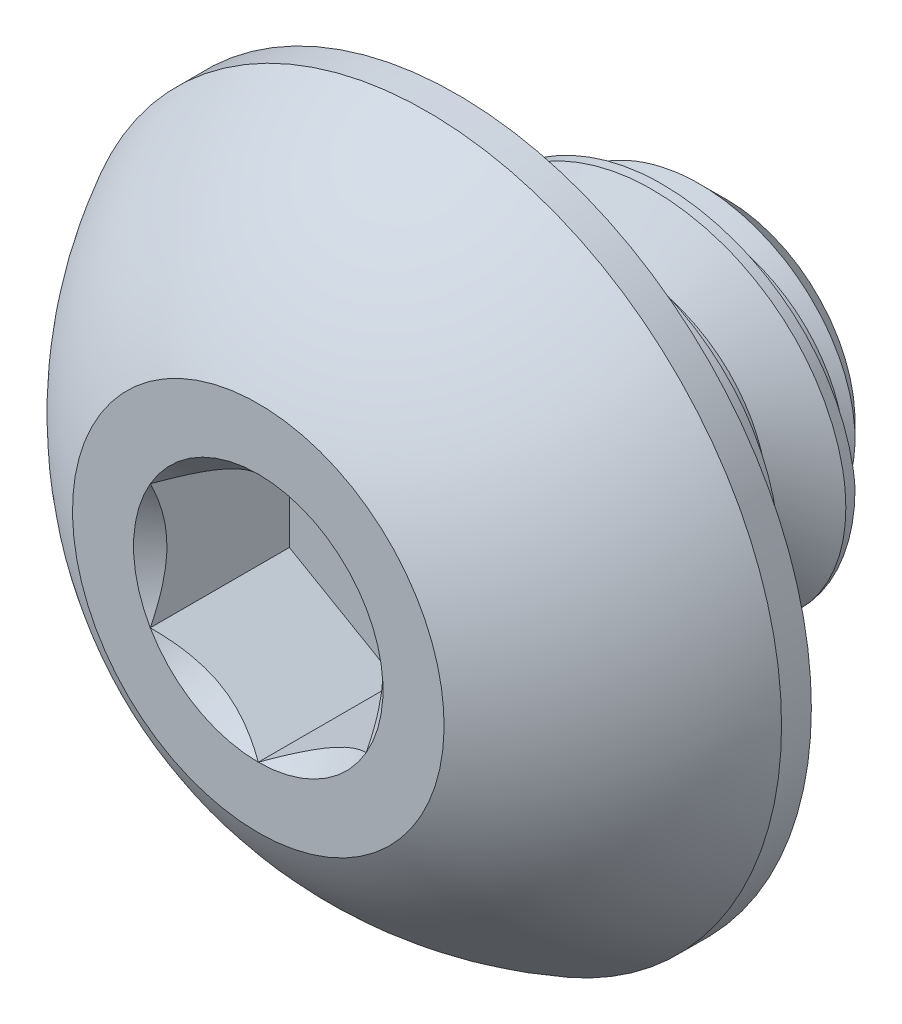
SolidWorks part; units mm, degrees
material "AISI 316 Annealed Stainless Steel Bar (SS)"
ref_plane "Front" through (0, 0, 0) normal (0, 0, 1) x (1, 0, 0)
ref_plane "Top" through (0, 0, 0) normal (0, 1, 0) x (1, 0, 0)
ref_plane "Right" through (0, 0, 0) normal (1, 0, 0) x (0, 0, -1)
sketch "Sketch1" plane through (0, 0, 0) normal (1, 0, 0) x (0, 0, -1)
  line L2 (1.1684, 1.0922) -> (2.7559, 1.0922)
  line L3 (2.7559, 1.0922) -> (2.7559, 0)
  line L4 (2.7559, 0) -> (1.1684, 0)
  line L6 (0.9931, 2.0828) -> (1.1684, 2.0828) construction
  line L7 (2.7559, 1.0922) -> (2.7559, -1.0922) construction
  line L8 (0, 0) -> (1.1684, 0) construction
  line L9 (1.1684, 2.0828) -> (1.1684, -2.0828) construction
  line L11 (1.1684, 1.0922) -> (1.1684, 0)
  line L13 (0, 0.635) -> (0, -0.635) construction
  line L14 (0, 0.635) -> (0, 1.0922) construction
  arc A3 (0, 1.0922) -> (0.9931, 2.0828) centre (2.08, 0) cw construction
  dimension "D1" = 0.1753
revolve "Revolve1" add sketch "Sketch1" angle 360 mid plane about L4
sketch "Sketch3" plane through (0, 0, -2.7559) normal (0, 0, -1) x (-1, 0, 0)
  circle A0 centre (0, 0) radius 1.0922
curve "Helix/Spiral1" pitch 0.4536 height 2.0411 radius 1.0922 centre (0, 0, -2.7559) axis (0, 0, 1) start towards (0, 1, 0)
sketch "Sketch2" plane through (0, 0, 0) normal (1, 0, 0) x (0, 0, -1)
  line L0 (2.7559, 1.0922) -> (3.1528, 1.0922)
  line L1 (3.1528, 1.0922) -> (2.9827, 0.7976)
  line L2 (2.9827, 0.7976) -> (2.926, 0.7976)
  line L3 (2.926, 0.7976) -> (2.7559, 1.0922)
  line L4 (2.8409, 0.9449) -> (3.0677, 0.9449) construction
  dimension "D1" = 60
  dimension "D2" = 0.0567
  dimension "D3" = 0.2268
chamfer "Chamfer1" distance 0.3402 angle 45 1 edges at (0, 1.0922, -2.7559)
sweep "Cut-Sweep1" cut profiles "Sketch2" path "Helix/Spiral1" align with end faces yes
sketch "Sketch7" plane through (0, 0, 0) normal (1, 0, 0) x (0, 0, -1)
  line L6 (0.9931, 2.0828) -> (1.1684, 2.0828) construction
  line L8 (0, 0) -> (1.1684, 0) construction
  line L11 (1.1684, 2.0828) -> (1.1684, -2.0828) construction
  line L12 (0.9931, 2.0828) -> (1.1684, 2.0828)
  line L13 (0, 0) -> (1.1684, 0)
  line L14 (0, 0.635) -> (0, -0.635) construction
  line L15 (1.1684, 2.0828) -> (1.1684, 0)
  line L16 (0, 1.0922) -> (0, 0)
  arc A2 (0.9931, 2.0828) -> (0, 1.0922) centre (2.08, 0) ccw construction
  arc A3 (0.9931, 2.0828) -> (0, 1.0922) centre (2.08, 0) ccw
revolve "Revolve2" add sketch "Sketch7" angle 360 mid plane about L13
sketch "Sketch5" plane through (0, 0, 0) normal (0, 0, 1) x (1, 0, 0)
  line L1 (0.635, -0.3666) -> (0.635, 0.3666)
  line L2 (0.635, 0.3666) -> (0, 0.7332)
  line L3 (0, 0.7332) -> (-0.635, 0.3666)
  line L4 (-0.635, 0.3666) -> (-0.635, -0.3666)
  line L5 (-0.635, -0.3666) -> (0, -0.7332)
  line L6 (0, -0.7332) -> (0.635, -0.3666)
  circle A0 centre (0, 0) radius 0.635 construction
extrude "Cut-Extrude2" cut sketch "Sketch5" against normal blind 0.8179
sketch "Sketch6" plane through (0, 0, 0) normal (0, 0, 1) x (1, 0, 0)
  circle A0 centre (0, 0) radius 0.7332
extrude "Cut-Extrude3" cut sketch "Sketch6" against normal blind 0.8179 draft 45
sketch "Sketch9" [suppressed] plane through (0, 0, -4.2164) normal (0, 0, 1) x (1, 0, 0)
  circle A2 centre (0, 0) radius 3.9687
extrude "Boss-Extrude2" [suppressed] add sketch "Sketch9" against normal offset from surface (9.525 mm away) 28.575 up to face at (0, 0.752, -2.7559)
sketch "Sketch10" plane through (0, 0, 0) normal (1, 0, 0) x (0, 0, -1)
  line L0 (2.7559, 1.0922) -> (2.7559, -1.0922) construction
  point P0 (2.0755, -1.0922)
  dimension "D1" = 0.6804
equation "\"D3@Helix/Spiral1\" = \"Lg@Sketch1\" + \"D4@Helix/Spiral1\""
equation "\"D2@Sketch2\" = \"D4@Helix/Spiral1\" * .125"
equation "\"D3@Sketch2\" = \"D4@Helix/Spiral1\" * .5"
equation "\"D1@Chamfer1\" = \"D4@Helix/Spiral1\" * .75"
equation "\"D1@Cut-Extrude2\" = \"Head Ht@Sketch1\" * .7"
equation "\"D1@Sketch1\" = \"Head Ht@Sketch1\" * .15"
equation "\"D1@Sketch10\" = \"D4@Helix/Spiral1\" * 1.5"
equation "\"D1@Cut-Extrude3\" = \"D1@Cut-Extrude2\""
